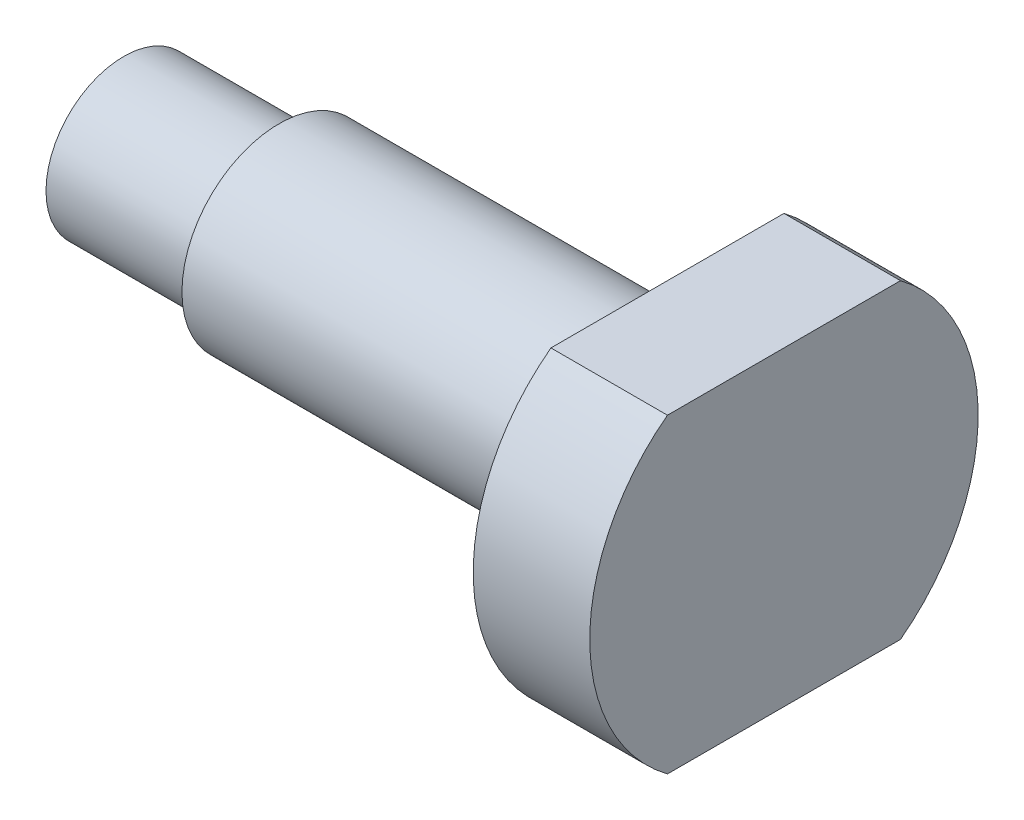
SolidWorks part; units mm, degrees
material "201 Annealed Stainless Steel (SS)"
ref_plane "Front Plane" through (0, 0, 0) normal (0, 0, 1) x (1, 0, 0)
ref_plane "Top Plane" through (0, 0, 0) normal (0, 1, 0) x (1, 0, 0)
ref_plane "Right Plane" through (0, 0, 0) normal (1, 0, 0) x (0, 0, -1)
sketch "Sketch2" plane through (0, 0, 0) normal (1, 0, 0) x (0, 0, -1)
  line L1 (3, 4) -> (-3, 4)
  line L2 (3, -4) -> (-3, -4)
  arc A0 (-3, 4) -> (-3, -4) centre (0, 0) ccw
  circle A1 centre (0, 0) radius 2.5
  circle A2 centre (0, 0) radius 2
  arc A3 (3, -4) -> (3, 4) centre (0, 0) ccw
  point P9 (-3.2245, 3.8213)
  dimension "D1" = 10
  dimension "D2" = 5
  dimension "D3" = 4
  dimension "D4" = 4
  dimension "8" = 8
extrude "Boss-Extrude1" add sketch "Sketch2" along normal blind 3 contours L2 A3 L1 A0 A1 | A1 A2 | A2 region at (0, 0, -4.8719) region at (0, 0, 2.4293) region at (0, 0, 0)
extrude "Boss-Extrude2" add sketch "Sketch2<3>" against normal blind 10 contours A1 A2 | A2 region at (0, 0, 2.4293) region at (0, 0, 0)
sketch "Sketch2<3>" plane through (0, 0, 0) normal (1, 0, 0) x (0, 0, -1) same geometry as "Sketch2"
sketch "Sketch3" plane through (-10, 0, 0) normal (-1, 0, 0) x (0, 0, 1)
  circle A0 centre (0, 0) radius 2 construction
  circle A1 centre (0, 0) radius 2
extrude "Boss-Extrude3" add sketch "Sketch3" along normal blind 4
cosmetic thread "Cosmetic Thread1" parameters "D2"=3.22
